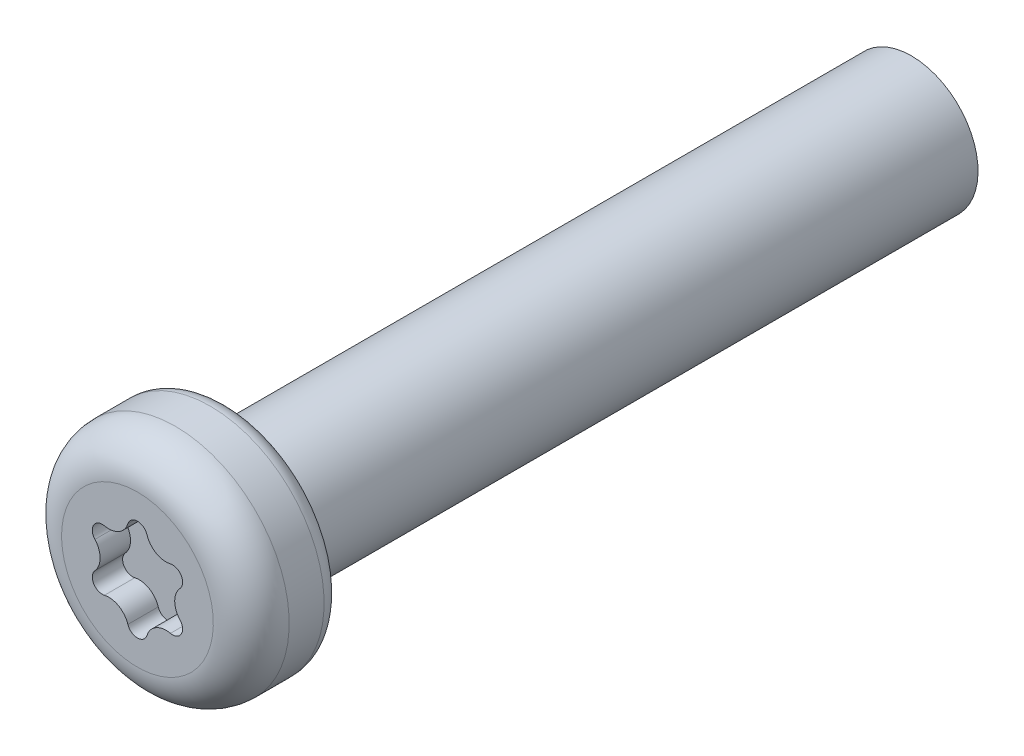
SolidWorks part; units mm, degrees
ref_plane "Front" through (0, 0, 0) normal (0, 0, 1) x (1, 0, 0)
ref_plane "Top" through (0, 0, 0) normal (0, 1, 0) x (1, 0, 0)
ref_plane "Right" through (0, 0, 0) normal (1, 0, 0) x (0, 0, -1)
sketch "Sketch17" plane through (0, 0, 0) normal (1, 0, 0) x (0, 0, -1)
  line L0 (12, 1.17) -> (12, -1.17) construction
  line L1 (0, 0) -> (12, 0)
  line L2 (0, 0) -> (0, 1.17)
  line L3 (0, 1.17) -> (12, 1.17)
  line L4 (12, 0) -> (12, 1.17)
  line L5 (11.298, 0.9224) -> (10.596, 1.0462) construction
  line L6 (10.596, 1.0462) -> (10.596, 1.17) construction
  line L7 (11.298, 0.9224) -> (12, 0.7987) construction
  line L8 (10.596, 1.0462) -> (9.894, 1.17) construction
  dimension "Body Length" = 12
  dimension "Dia" = 2.34
  dimension "D2" = 1.404
  dimension "D1" = 10
revolve "Revolve1" add sketch "Sketch17" angle 360 about L11
sketch "Sketch23" plane through (0, 0, -12) normal (0, 0, -1) x (-1, 0, 0)
  circle A1 centre (0, 0) radius 1.17
  circle A2 centre (0, 0) radius 1.17
  dimension "D1" = 0
curve "Helix/Spiral1" pitch 0.91 height 13.6 turns 14.9451
sketch "Sketch21" plane through (0, 0, 0) normal (1, 0, 0) x (0, 0, -1)
  line L0 (12, 1.17) -> (12.8645, 1.17)
  line L1 (12.8645, 1.17) -> (12.5943, 0.702)
  line L2 (12.5943, 0.702) -> (12.2702, 0.702)
  line L3 (12.2702, 0.702) -> (12, 1.17)
  dimension "D1" = 60
  dimension "D2" = 0.8645
  dimension "D3" = 0.468
sweep "Cut-Sweep1" [suppressed] cut profiles "Sketch21" path "Helix/Spiral1"
sketch "Sketch18" [suppressed] plane through (0, 0, 0) normal (0, 0, -1) x (-1, 0, 0)
  line L0 (0, 1.17) -> (0, 0) construction
  line L1 (0, 0) -> (-1.0132, -0.585) construction
  line L2 (0, 0) -> (1.0132, -0.585) construction
  circle A0 centre (0, 0) radius 1.17 construction
  arc A1 (-0.234, 1.1073) -> (0.234, 1.1073) centre (0, 0.702) cw
  arc A2 (-1.0759, -0.351) -> (-0.8419, -0.7563) centre (-0.6079, -0.351) ccw
  arc A3 (1.0759, -0.351) -> (0.8419, -0.7563) centre (0.6079, -0.351) cw
  arc A4 (-0.234, 1.1073) -> (-1.0759, -0.351) centre (0.608, -0.3511) ccw
  arc A5 (0.234, 1.1073) -> (1.0759, -0.351) centre (-0.608, -0.3511) cw
  arc A6 (-0.8419, -0.7563) -> (0.8419, -0.7563) centre (0, 0.7021) ccw
  dimension "D3" = 0.468
  dimension "D1" = 120
  dimension "D2" = 120
  dimension "D4" = 0.0001
extrude "Cut-Extrude3" [suppressed] cut sketch "Sketch18" along normal through all flip side to cut
ref_plane "Plane1" through (0, 0, -9.894) normal (0, 0, 1) x (1, 0, 0)
sketch "Sketch24" [suppressed] plane through (0, 0, -9.894) normal (0, 0, 1) x (1, 0, 0)
  arc A6 (-1.0759, -0.351) -> (-0.8419, -0.7563) centre (-0.6079, -0.351) ccw
  arc A7 (-0.234, 1.1073) -> (-1.0759, -0.351) centre (0.608, -0.3511) ccw
  arc A8 (0.234, 1.1073) -> (-0.234, 1.1073) centre (0, 0.702) ccw
  arc A9 (1.0759, -0.351) -> (0.234, 1.1073) centre (-0.608, -0.3511) ccw
  arc A10 (0.8419, -0.7563) -> (1.0759, -0.351) centre (0.6079, -0.351) ccw
  arc A11 (-0.8419, -0.7563) -> (0.8419, -0.7563) centre (0, 0.7021) ccw
  arc A12 (-1.0759, -0.351) -> (-0.8419, -0.7563) centre (-0.6079, -0.351) ccw
  arc A13 (-0.234, 1.1073) -> (-1.0759, -0.351) centre (0.608, -0.3511) ccw
  arc A14 (0.234, 1.1073) -> (-0.234, 1.1073) centre (0, 0.702) ccw
  arc A15 (1.0759, -0.351) -> (0.234, 1.1073) centre (-0.608, -0.3511) ccw
  arc A16 (0.8419, -0.7563) -> (1.0759, -0.351) centre (0.6079, -0.351) ccw
  arc A17 (-0.8419, -0.7563) -> (0.8419, -0.7563) centre (0, 0.7021) ccw
  dimension "D1" = 0
sketch "Sketch1" plane through (0, 0, 0) normal (0, 0, 1) x (1, 0, 0)
  circle A0 centre (0, 0) radius 2
  dimension "Head Dia" = 4
extrude "Cut-Extrude6" [suppressed] cut sketch "Sketch24" against normal through all draft 7 flip side to cut draft outward yes
extrude "Extrude3" add sketch "Sketch1" along normal blind 1.6
sketch "Sketch11" plane through (0, 0, 0) normal (1, 0, 0) x (0, 0, -1)
  line L2 (-1.6, 2) -> (-1.6, -2) construction
  line L4 (0, 2) -> (-1.6, 2) construction
  line L5 (-0.9333, 2) -> (-0.32, 2)
  line L6 (0, -2) -> (0, 2) construction
  line L7 (-1.6, 2) -> (-1.6, 1.3333) construction
  line L8 (-1.6, 0.6667) -> (-1.6, 0) construction
  line L9 (-1.6, 1.3333) -> (-1.6, 0.6667) construction
  line L10 (-1.6, 1.3333) -> (-1.854, 1.3333)
  line L11 (0, 0) -> (-1.6, 0) construction
  line L12 (-1.854, 1.3333) -> (-1.854, 2.254)
  line L13 (-1.854, 2.254) -> (0.254, 2.254)
  line L14 (0.254, 2.254) -> (0.254, 1.68)
  line L15 (0.254, 1.68) -> (0, 1.68)
  arc A0 (-1.6, 1.3333) -> (-0.9333, 2) centre (-0.9333, 1.3333) cw
  arc A1 (-0.32, 2) -> (0, 1.68) centre (-0.32, 1.68) cw
  dimension "D1" = 0.32
  dimension "D2" = 0.254
  dimension "D3" = 0.254
revolve "Cut-Revolve3" cut sketch "Sketch11" angle 360 about L11
sketch "Sketch12" plane through (0, 0, 1.6) normal (0, 0, 1) x (1, 0, 0)
  line L0 (0, 0) -> (0, 0.8889) construction
  line L1 (0, 0) -> (0.3275, 0.5672) construction
  line L2 (0, 0) -> (-0.3275, 0.5672) construction
  line L3 (-0.3275, 0.5672) -> (0, 0)
  line L4 (0, 0) -> (0.3275, 0.5672)
  arc A0 (-0.3275, 0.5672) -> (-0.1678, 0.7659) centre (-0.5035, 0.872) ccw
  arc A1 (-0.1678, 0.7659) -> (0.1678, 0.7659) centre (0, 0.7129) cw
  arc A2 (0.1678, 0.7659) -> (0.3275, 0.5672) centre (0.5035, 0.872) ccw
  circle A5 centre (0, 0) radius 0.8889 construction
  dimension "M" = 1.7778
  dimension "D2" = 0.176
  dimension "D3" = 0.352
  dimension "D1" = 60
extrude "Cut-Extrude1" cut sketch "Sketch12" against normal blind 0.5333
ref_axis "Axis1" through (0, 0, 1.6) along (0, 0, -1)
pattern_circular "CirPattern1" count 6 over 360 of "Cut-Extrude1"
combine bodies "Combine1" operation type add bodies to combine 143 141
sketch "Sketch19" plane through (0, 0, 0) normal (1, 0, 0) x (0, 0, -1)
  line L0 (6, 1.17) -> (6, -1.17) construction
  line L3 (0, 0) -> (12, 0) construction
  line L4 (12, 1.17) -> (12, -1.17) construction
  point P0 (-1.6, 1.3333)
  point P1 (0, 1.68)
  point P2 (6, 0)
sketch "Sketch20" plane through (0, 0, 0) normal (0, 0, 1) x (1, 0, 0)
  point P0 (0.5794, -0.5283)
equation "\"D1@Cut-Extrude1\"=\"Head Ht@Extrude3\"/3"
equation "\"D1@Sketch11\" = \"Head Ht@Extrude3\"/5"
equation "\"M@Sketch12\" = \"Head Dia@Sketch1\"/2.25"
equation "\"D2@Sketch12\" = \"Head Dia@Sketch1\" * .044"
equation "\"D3@Sketch12\" = \"D2@Sketch12\" * 2"
equation "\"D3@Helix/Spiral1\" = \"Body Length@Sketch17\" + \"Head Ht@Extrude3\""
equation "\"D2@Sketch21\" = \"D4@Helix/Spiral1\" -  ( \"D4@Helix/Spiral1\" * .05 ) "
equation "\"D3@Sketch21\" = \"Dia@Sketch17\" * .2"
equation "\"D3@Sketch18\" = \"Dia@Sketch17\" * .2"
equation "\"D2@Sketch17\" = \"Dia@Sketch17\" * .6"
